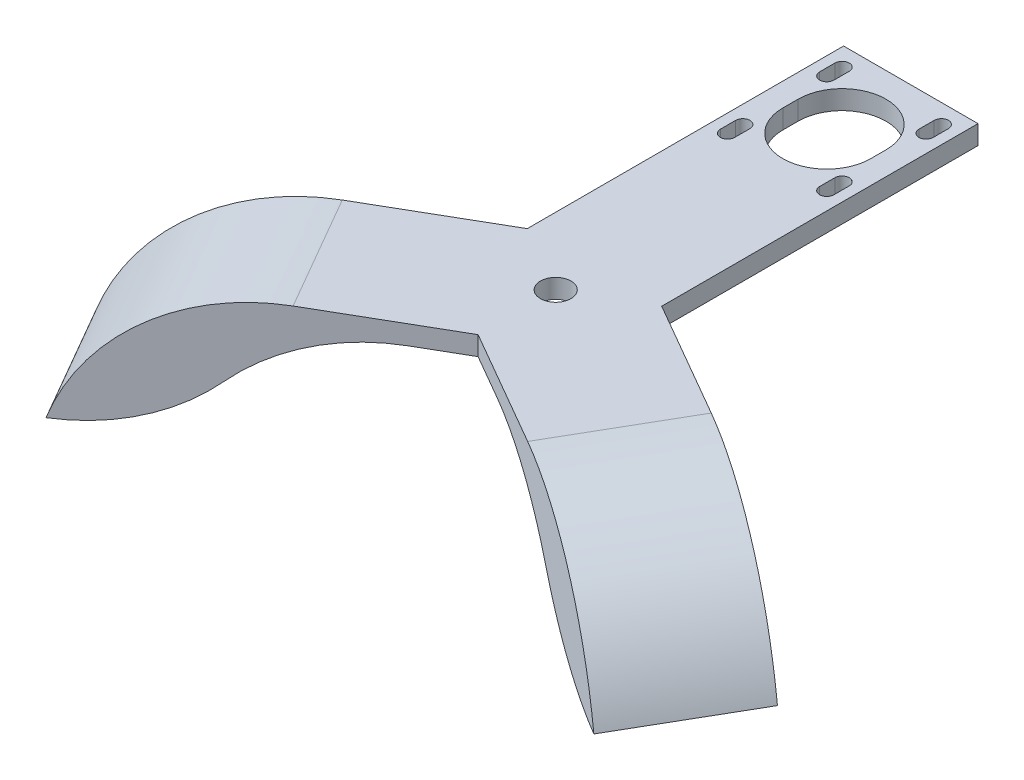
SolidWorks part; units mm, degrees
ref_plane "Front Plane" through (0, 0, 0) normal (0, 0, 1) x (1, 0, 0)
ref_plane "Top Plane" through (0, 0, 0) normal (0, 1, 0) x (1, 0, 0)
ref_plane "Right Plane" through (0, 0, 0) normal (1, 0, 0) x (0, 0, -1)
sketch "Sketch1" plane through (0, 0, 0) normal (0, 1, 0) x (1, 0, 0)
  line L0 (-17.6, 10.1614) -> (-17.6, 93)
  line L1 (17.6, 10.1614) -> (17.6, 93)
  line L2 (0, 0) -> (0, 75) construction
  line L3 (-11.5, 75) -> (-11.5, 71)
  line L4 (11.5, 75) -> (11.5, 71)
  line L5 (-13, 88) -> (-13, 62) construction
  line L6 (13, 88) -> (13, 62) construction
  line L7 (-13, 62) -> (13, 62) construction
  line L8 (-13, 88) -> (13, 88) construction
  line L9 (-14.875, 88) -> (-14.875, 84)
  line L10 (-11.125, 88) -> (-11.125, 84)
  line L11 (11.125, 88) -> (11.125, 84)
  line L12 (14.875, 88) -> (14.875, 84)
  line L13 (11.125, 62) -> (11.125, 58)
  line L14 (14.875, 62) -> (14.875, 58)
  line L15 (-14.875, 62) -> (-14.875, 58)
  line L16 (-11.125, 62) -> (-11.125, 58)
  line L17 (17.6, 93) -> (-17.6, 93)
  line L18 (17.6, 10.1614) -> (89.3404, -31.258)
  line L19 (0, -20.3227) -> (71.7404, -61.742)
  line L20 (71.7404, -61.742) -> (89.3404, -31.258)
  line L21 (0, -20.3227) -> (-71.7404, -61.742)
  line L22 (-17.6, 10.1614) -> (-89.3404, -31.258)
  line L23 (-89.3404, -31.258) -> (-71.7404, -61.742)
  circle A0 centre (0, 0) radius 60 construction
  circle A1 centre (0, 0) radius 17.6 construction
  circle A2 centre (0, 75) radius 15 construction
  arc A3 (11.5, 75) -> (-11.5, 75) centre (0, 75) ccw
  arc A4 (-11.5, 71) -> (11.5, 71) centre (0, 71) ccw
  arc A5 (-11.125, 88) -> (-14.875, 88) centre (-13, 88) ccw
  arc A6 (14.875, 88) -> (11.125, 88) centre (13, 88) ccw
  arc A7 (14.875, 62) -> (11.125, 62) centre (13, 62) ccw
  arc A8 (-11.125, 62) -> (-14.875, 62) centre (-13, 62) ccw
  arc A9 (-14.875, 84) -> (-11.125, 84) centre (-13, 84) ccw
  arc A10 (11.125, 84) -> (14.875, 84) centre (13, 84) ccw
  arc A11 (11.125, 58) -> (14.875, 58) centre (13, 58) ccw
  arc A12 (-14.875, 58) -> (-11.125, 58) centre (-13, 58) ccw
  circle A13 centre (0, 0) radius 4
  point P29 (0, 75)
  point P54 (0, 0)
  dimension "D1" = 35.2
  dimension "D3" = 120
  dimension "D4" = 4
  dimension "D9" = 3.75
  dimension "D2" = 75
  dimension "D5" = 26
  dimension "D6" = 13
  dimension "D7" = 26
  dimension "D8" = 13
  dimension "D12" = 18
  dimension "D11" = 2
  dimension "D10" = 4
  dimension "D13" = 3
extrude "Boss-Extrude1" add sketch "Sketch1" along normal blind 5
sketch "Sketch2" plane through (0, 0, 0) normal (0, -1, 0) x (1, 0, 0)
  line L0 (-71.7404, 61.742) -> (-89.3404, 31.258)
  line L1 (-89.3404, 31.258) -> (-68.5558, 19.258)
  line L2 (-17.6, -10.1614) -> (-89.3404, 31.258) construction
  line L3 (-68.5558, 19.258) -> (-50.9558, 49.742)
  line L4 (-71.7404, 61.742) -> (0, 20.3227) construction
  line L5 (-50.9558, 49.742) -> (-71.7404, 61.742)
  line L6 (71.7404, 61.742) -> (89.3404, 31.258)
  line L7 (89.3404, 31.258) -> (68.5558, 19.258)
  line L8 (89.3404, 31.258) -> (17.6, -10.1614) construction
  line L9 (68.5558, 19.258) -> (50.9558, 49.742)
  line L10 (0, 20.3227) -> (71.7404, 61.742) construction
  line L11 (50.9558, 49.742) -> (71.7404, 61.742)
  dimension "D1" = 24
  dimension "D2" = 24
extrude "Boss-Extrude2" add sketch "Sketch2" along normal blind 29
fillet "Fillet1" radius 50 4 edges at (-59.7558, 0, 34.5) (59.7558, 0, 34.5) (80.5404, 5, 46.5) (-80.5404, 5, 46.5)
fillet "Fillet2" radius 50 2 edges at (-59.7558, -29, 34.5) (59.7558, -29, 34.5)
